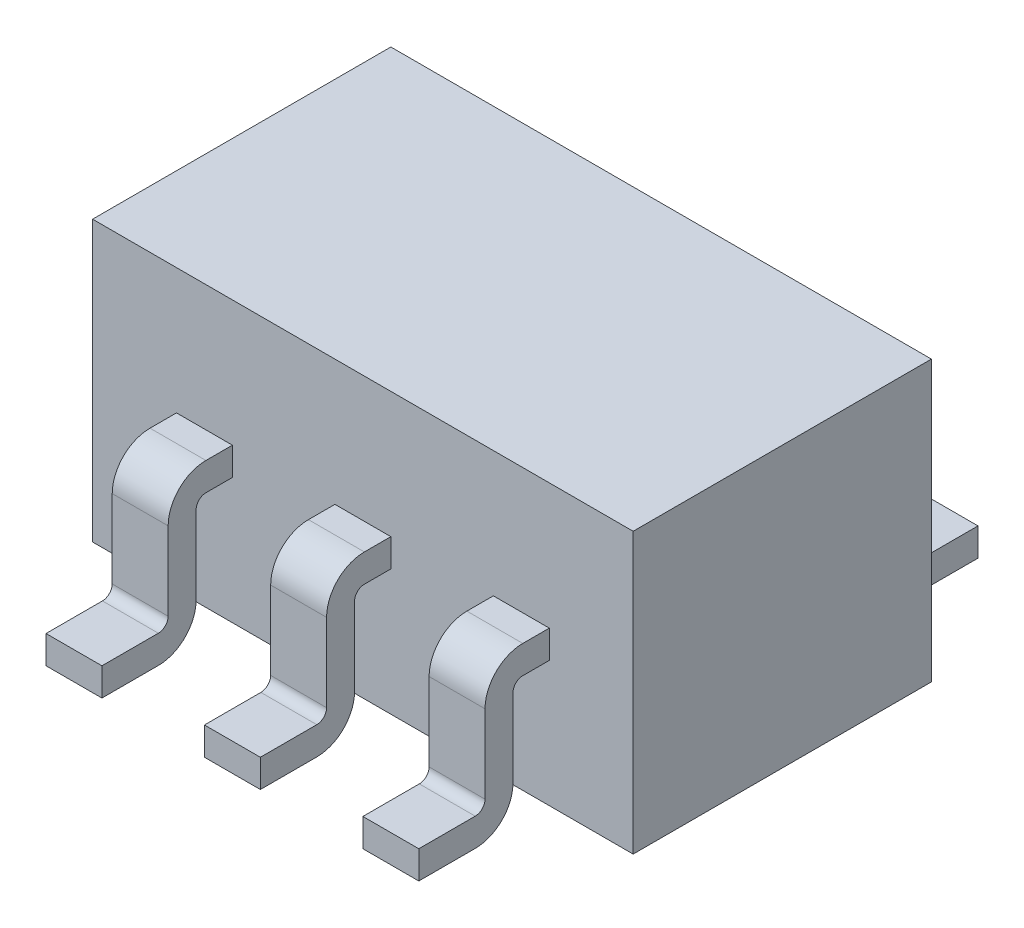
SolidWorks part; units mm, degrees
ref_plane "Front Plane" through (0, 0, 0) normal (0, 0, 1) x (1, 0, 0)
ref_plane "Top Plane" through (0, 0, 0) normal (0, 1, 0) x (1, 0, 0)
ref_plane "Right Plane" through (0, 0, 0) normal (1, 0, 0) x (0, 0, -1)
sketch "Sketch1" plane through (0, 0, 0) normal (0, 1, 0) x (1, 0, 0)
  line L1 (0, 0) -> (2.9, 0)
  line L2 (0, 0) -> (0, 1.6)
  line L3 (0, 1.6) -> (2.9, 1.6)
  line L4 (2.9, 0) -> (2.9, 1.6)
extrude "Boss-Extrude1" add sketch "Sketch1" along normal blind 1.5
ref_plane "Plane2" through (0.6768, 0, -1.2266) normal (0.4831, 0, -0.8756) x (-0.8756, 0, -0.4831)
ref_plane "Plane1" through (0, 0, 0) normal (0.4831, 0, 0.8756) x (0.8756, 0, -0.4831)
ref_axis "Axis1" through (1.45, -0.5072, -0.8) along (0, 1, 0)
sketch "Sketch2" plane through (0, 0, 0) normal (0, 0, 1) x (1, 0, 0)
  line L0 (0.6, 1.5) -> (0.6, 0.825) construction
  line L1 (0.45, 0.825) -> (0.75, 0.825)
  line L2 (0.45, 0.825) -> (0.45, 0.675)
  line L3 (0.45, 0.675) -> (0.75, 0.675)
  line L4 (0.75, 0.825) -> (0.75, 0.675)
  line L5 (0, 1.5) -> (2.9, 1.5) construction
  line L6 (1.3, 0.825) -> (1.6, 0.825)
  line L7 (0.6, 0.675) -> (0.6, 0) construction
  line L8 (0, 0) -> (2.9, 0) construction
  line L9 (1.3, 0.825) -> (1.3, 0.675)
  line L10 (0.45, 0.75) -> (0, 0.75) construction
  line L11 (0, 1.5) -> (0, 0) construction
  line L12 (1.3, 0.675) -> (1.6, 0.675)
  line L13 (1.6, 0.825) -> (1.6, 0.675)
  line L14 (2.15, 0.825) -> (2.45, 0.825)
  line L15 (2.15, 0.825) -> (2.15, 0.675)
  line L16 (2.15, 0.675) -> (2.45, 0.675)
  line L17 (2.45, 0.825) -> (2.45, 0.675)
  line L18 (2.45, 0.75) -> (2.9, 0.75) construction
  line L19 (2.9, 1.5) -> (2.9, 0) construction
  dimension "D1" = 3
sketch "Sketch3" plane through (0, 0, 0) normal (1, 0, 0) x (0, 0, -1)
  line L0 (0, 0.75) -> (-0.1421, 0.75)
  line L1 (0, 0.825) -> (0, 0.675) construction
  line L2 (-0.2697, 0.6223) -> (-0.2697, 0.2027)
  line L3 (-0.3974, 0.075) -> (-0.7, 0.075)
  line L4 (-0.1421, 0.75) -> (-0.1421, 0.6223) construction
  line L5 (-0.1421, 0.6223) -> (-0.2697, 0.6223) construction
  line L6 (-0.2697, 0.2027) -> (-0.3974, 0.2027) construction
  line L7 (-0.3974, 0.2027) -> (-0.3974, 0.075) construction
  arc A0 (-0.1421, 0.75) -> (-0.2697, 0.6223) centre (-0.1421, 0.6223) ccw
  arc A1 (-0.2697, 0.2027) -> (-0.3974, 0.075) centre (-0.3974, 0.2027) cw
sweep "Sweep3" add profiles "Sketch2" path "Sketch3"
pattern_circular "CirPattern1" count 2 every 180 about axis through (1.45, -0.5072, -0.8) along (0, 1, 0) of "Sweep3"
